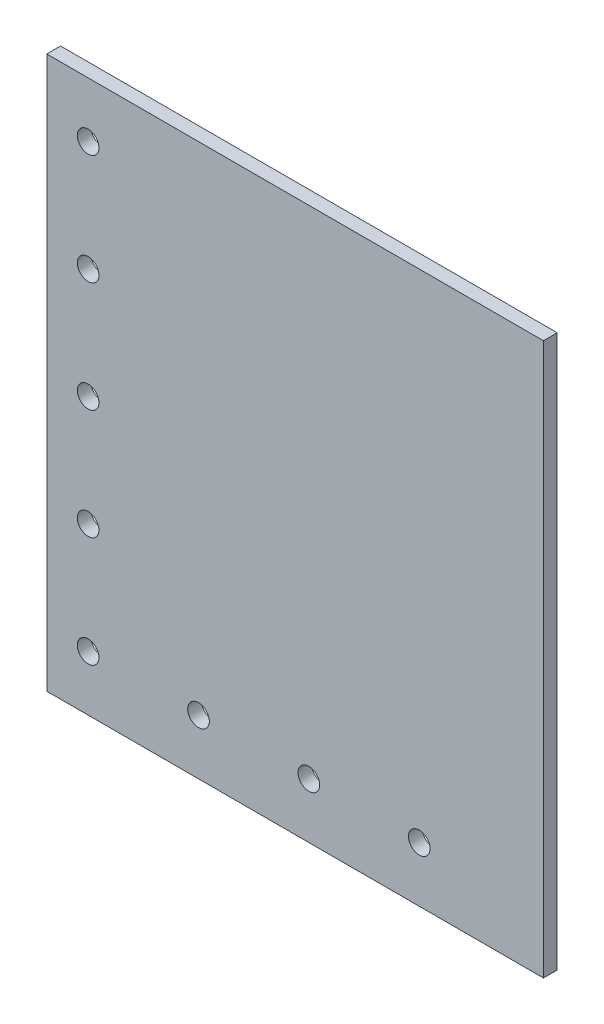
SolidWorks part; units mm, degrees
material "6061-T6 (SS)"
ref_plane "Front Plane" through (0, 0, 0) normal (0, 0, 1) x (1, 0, 0)
ref_plane "Top Plane" through (0, 0, 0) normal (0, 1, 0) x (1, 0, 0)
ref_plane "Right Plane" through (0, 0, 0) normal (1, 0, 0) x (0, 0, -1)
sketch "Sketch1" plane through (0, 0, 0) normal (0, 0, 1) x (1, 0, 0)
  line L0 (0, 127) -> (0, 0)
  line L1 (0, 0) -> (114.3, 0)
  line L2 (114.3, 0) -> (114.3, 25.4)
  line L5 (0, 127) -> (114.3, 127)
  line L6 (114.3, 127) -> (114.3, 25.4)
  circle A0 centre (111.125, 12.7) radius 2.4892 construction
  circle A1 centre (85.725, 12.7) radius 2.4892
  circle A2 centre (60.325, 12.7) radius 2.4892
  circle A3 centre (34.925, 12.7) radius 2.4892
  circle A4 centre (9.525, 12.7) radius 2.4892
  circle A5 centre (9.525, 38.1) radius 2.4892
  circle A6 centre (9.525, 63.5) radius 2.4892
  circle A7 centre (9.525, 88.9) radius 2.4892
  circle A8 centre (9.525, 114.3) radius 2.4892
  point P9 (114.3, 12.7)
  dimension "D5" = 4.9784
  dimension "D8" = 25.4
  dimension "D10" = 25.4
  dimension "D2" = 9.525
  dimension "D1" = 25.4
  dimension "D3" = 114.3
  dimension "D4" = 127
  dimension "D7" = 5
  dimension "D9" = 5
extrude "Boss-Extrude1" add sketch "Sketch1" along normal mid plane 3.175
